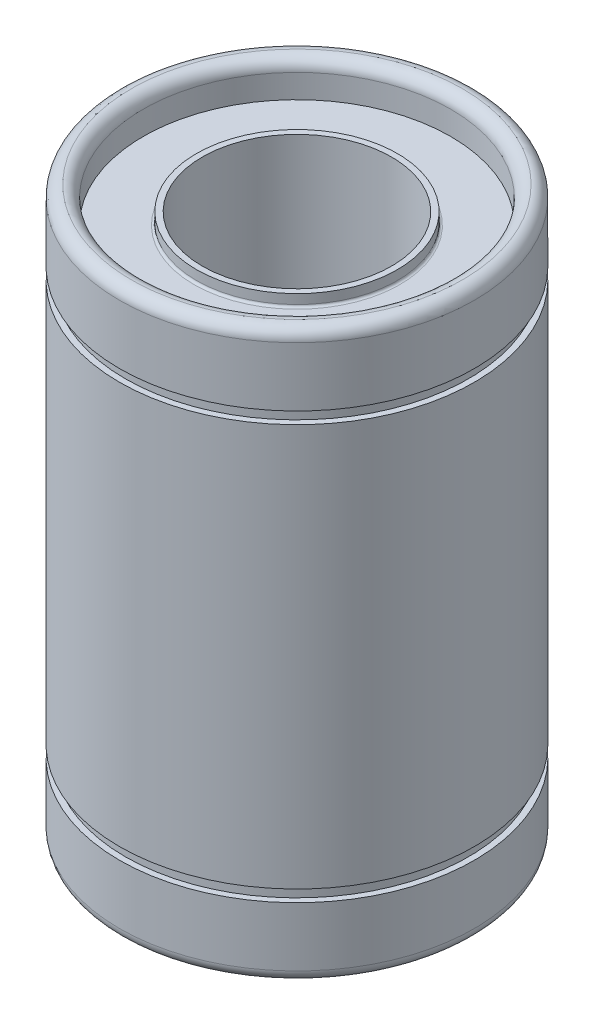
SolidWorks part; units mm, degrees
material "Plain Carbon Steel"
ref_plane "Front Plane" through (0, 0, 0) normal (0, 0, 1) x (1, 0, 0)
ref_plane "Top Plane" through (0, 0, 0) normal (0, 1, 0) x (1, 0, 0)
ref_plane "Right Plane" through (0, 0, 0) normal (1, 0, 0) x (0, 0, -1)
sketch "Sketch1" plane through (0, 0, 0) normal (0, 0, 1) x (1, 0, 0)
  line L0 (0, 24) -> (0, 0)
  line L1 (0, 24) -> (7.5, 24)
  line L2 (7.5, 24) -> (7.5, 21)
  line L3 (7.5, 21) -> (7.25, 21)
  line L4 (7.25, 21) -> (7.25, 20.5)
  line L5 (7.25, 20.5) -> (7.5, 20.5)
  line L6 (7.5, 20.5) -> (7.5, 3.5)
  line L7 (7.5, 3.5) -> (7.25, 3.5)
  line L8 (7.25, 3.5) -> (7.25, 3)
  line L9 (7.25, 3) -> (7.5, 3)
  line L10 (7.5, 3) -> (7.5, 0)
  line L11 (7.5, 0) -> (0, 0)
  dimension "D1" = 24
  dimension "D2" = 7.5
  dimension "D3" = 0.25
  dimension "D4" = 0.25
  dimension "D5" = 0.5
  dimension "D6" = 0.5
  dimension "D7" = 3
  dimension "D8" = 3
revolve "Revolve1" add sketch "Sketch1" angle 360 about L0
sketch "Sketch2" plane through (0, 24, 0) normal (0, 1, 0) x (1, 0, 0)
  circle A0 centre (0, 0) radius 6.5
  circle A1 centre (0, 0) radius 7.5 construction
  dimension "D1" = 1
extrude "Cut-Extrude1" cut sketch "Sketch2" against normal blind 1.5
sketch "Sketch3" plane through (0, 0, 0) normal (0, -1, 0) x (1, 0, 0)
  circle A0 centre (0, 0) radius 6.5
  circle A1 centre (0, 0) radius 7.5 construction
  dimension "D1" = 1
extrude "Cut-Extrude2" cut sketch "Sketch3" against normal blind 1.5
sketch "Sketch4" plane through (0, 22.5, 0) normal (0, 1, 0) x (1, 0, 0)
  circle A0 centre (0, 0) radius 4
  dimension "D1" = 8
extrude "Cut-Extrude3" cut sketch "Sketch4" against normal through all
sketch "Sketch5" plane through (0, 22.5, 0) normal (0, 1, 0) x (1, 0, 0)
  circle A0 centre (0, 0) radius 4
  circle A1 centre (0, 0) radius 4.25
  dimension "D1" = 0.25
extrude "Boss-Extrude1" add sketch "Sketch5" along normal blind 0.5
ref_plane "Plane1" through (0, 12, 0) normal (0, 1, 0) x (1, 0, 0)
mirror "Mirror1" about plane through (0, 12, 0) normal (0, 1, 0) of "Boss-Extrude1"
fillet "Fillet2" radius 0.5 2 edges at (0, 24, 7.5) (0, 24, 6.5)
fillet "Fillet3" radius 0.5 2 edges at (0, 0, 7.5) (0, 0, -6.5)
fillet "Fillet4" radius 0.1 2 edges at (0, 1.5, -4.25) (0, 22.5, 4.25)
